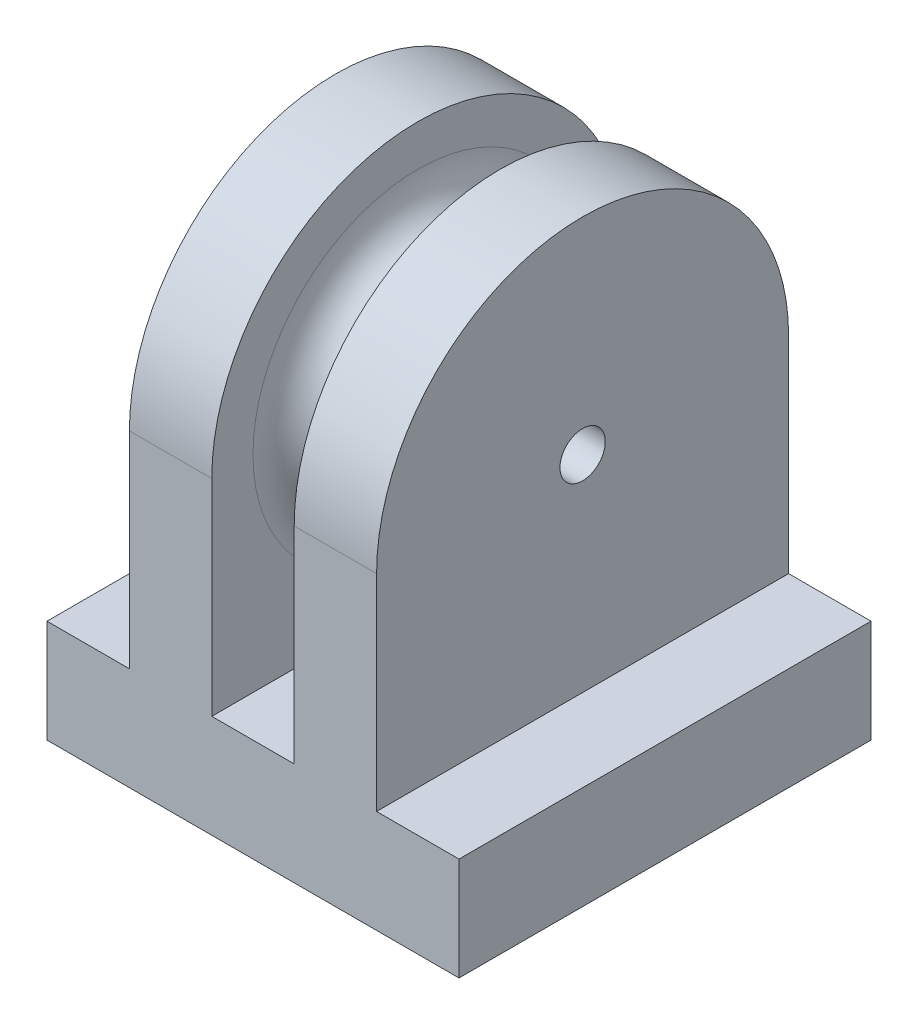
SolidWorks part; units mm, degrees
ref_plane "Front Plane" through (0, 0, 0) normal (0, 0, 1) x (1, 0, 0)
ref_plane "Top Plane" through (0, 0, 0) normal (0, 1, 0) x (1, 0, 0)
ref_plane "Right Plane" through (0, 0, 0) normal (1, 0, 0) x (0, 0, -1)
sketch "Sketch1" plane through (0, 0, 0) normal (0, 1, 0) x (1, 0, 0)
  line L1 (0, 0) -> (20, 0)
  line L2 (0, 0) -> (0, 20)
  line L3 (0, 20) -> (20, 20)
  line L4 (20, 0) -> (20, 20)
  dimension "D1" = 20
  dimension "D2" = 20
extrude "Boss-Extrude1" add sketch "Sketch1" along normal blind 5
sketch "Sketch3" plane through (0, 5, 0) normal (0, 1, 0) x (1, 0, 0)
  line L0 (20, 20) -> (0, 20) construction
  line L1 (4, 20) -> (8, 20)
  line L2 (4, 20) -> (4, 0)
  line L3 (4, 0) -> (8, 0)
  line L4 (8, 20) -> (8, 0)
  line L5 (0, 0) -> (20, 0) construction
  line L6 (0, 20) -> (0, 0) construction
  line L7 (12, 20) -> (16, 20)
  line L8 (12, 20) -> (12, 0)
  line L9 (12, 0) -> (16, 0)
  line L10 (16, 20) -> (16, 0)
  line L11 (20, 0) -> (20, 20) construction
  dimension "D1" = 4
  dimension "D2" = 4
  dimension "D3" = 4
  dimension "D4" = 4
extrude "Boss-Extrude2" add sketch "Sketch3" along normal blind 10
sketch "Sketch4" plane through (4, 0, 0) normal (-1, 0, 0) x (0, 0, 1)
  line L0 (-20, 15) -> (0, 15) construction
  circle A0 centre (-10, 15) radius 10
  point P5 (0, 0)
extrude "Boss-Extrude3" add sketch "Sketch4" against normal blind 4
sketch "Sketch5" plane through (16, 0, 0) normal (1, 0, 0) x (0, 0, -1)
  line L0 (0, 15) -> (20, 15) construction
  circle A0 centre (10, 15) radius 10
extrude "Boss-Extrude4" add sketch "Sketch5" against normal blind 4
sketch "Sketch6" plane through (4, 0, 0) normal (-1, 0, 0) x (0, 0, 1)
  circle A0 centre (-10, 15) radius 1.1
  dimension "D1" = 2.2
extrude "Cut-Extrude1" cut sketch "Sketch6" against normal through all
sketch "Sketch7" plane through (0, 5, 0) normal (0, 1, 0) x (1, 0, 0)
  line L0 (8, 0) -> (12, 0) construction
  line L1 (8, 0) -> (8, 20) construction
  line L2 (0, 10) -> (20, 10) construction
  line L3 (0, 20) -> (0, 0) construction
  line L4 (20, 0) -> (20, 20) construction
  circle A0 centre (10, 4) radius 0.5
  circle A1 centre (10, 16) radius 0.5
  point P12 (0, 0)
  dimension "D1" = 1
  dimension "D2" = 4
  dimension "D3" = 2
extrude "Cut-Extrude2" cut sketch "Sketch7" against normal through all
sketch "Sketch9" plane through (8, 0, 0) normal (1, 0, 0) x (0, 0, -1)
  circle A0 centre (10, 15) radius 6
  dimension "D1" = 12
extrude "Boss-Extrude5" add sketch "Sketch9" along normal blind 4
sketch "Sketch10" plane through (8, 0, 0) normal (1, 0, 0) x (0, 0, -1)
  circle A0 centre (10, 15) radius 3.5
  dimension "D1" = 7
extrude "Cut-Extrude3" cut sketch "Sketch10" along normal blind 4
fillet "Fillet1" radius 2 2 edges at (8, 15, -4) (12, 15, -16)
